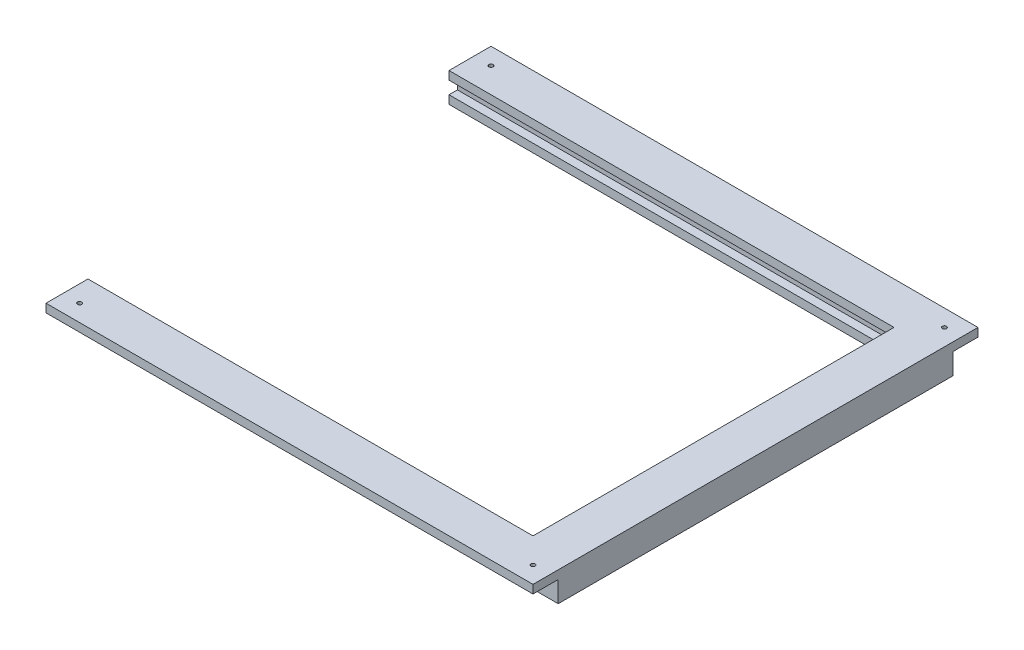
SolidWorks part; units mm, degrees
ref_plane "Спереди" through (0, 0, 0) normal (0, 0, 1) x (1, 0, 0)
ref_plane "Сверху" through (0, 0, 0) normal (0, 1, 0) x (1, 0, 0)
ref_plane "Справа" through (0, 0, 0) normal (1, 0, 0) x (0, 0, -1)
sketch "Эскиз1" plane through (0, 0, 0) normal (0, 1, 0) x (1, 0, 0)
  line L0 (50, -77.9215) -> (50, -607.9215)
  line L1 (-530, -77.9215) -> (50, -77.9215)
  line L2 (-530, -77.9215) -> (-530, -127.9215)
  line L3 (-530, -607.9215) -> (50, -607.9215)
  line L5 (-530, -127.9215) -> (0, -127.9215)
  line L7 (-530, -557.9215) -> (0, -557.9215)
  line L13 (-530, -557.9215) -> (-530, -607.9215)
  line L22 (0, -127.9215) -> (0, -557.9215)
  dimension "D1" = 580
  dimension "D12" = 50
  dimension "D2" = 530
  dimension "D3" = 50
  dimension "D4" = 50
  dimension "D9" = 50
  dimension "D8" = 77.9215
extrude "Бобышка-Вытянуть2" add sketch "Эскиз1" along normal blind 10
sketch "Эскиз2" plane through (0, 0, 0) normal (0, -1, 0) x (1, 0, 0)
  line L0 (-530, 127.9215) -> (0, 127.9215) construction
  line L5 (50, 607.9215) -> (50, 77.9215) construction
  line L6 (0, 557.9215) -> (-530, 557.9215) construction
  line L18 (50, 577.9215) -> (50, 107.9215)
  line L20 (10, 567.9215) -> (10, 117.9215)
  line L21 (-530, 77.9215) -> (-530, 127.9215) construction
  line L22 (50, 107.9215) -> (-530, 107.9215)
  line L24 (10, 117.9215) -> (-530, 117.9215)
  line L25 (-530, 107.9215) -> (-530, 117.9215)
  line L26 (-530, 557.9215) -> (-530, 607.9215) construction
  line L27 (50, 577.9215) -> (-530, 577.9215)
  line L29 (10, 567.9215) -> (-530, 567.9215)
  line L30 (-530, 577.9215) -> (-530, 567.9215)
  dimension "D1" = 40
  dimension "D2" = 10
  dimension "D3" = 10
  dimension "D4" = 10
  dimension "D5" = 10
extrude "Бобышка-Вытянуть3" add sketch "Эскиз2" along normal blind 15
sketch "Эскиз4" plane through (0, 10, 0) normal (0, 1, 0) x (1, 0, 0)
  line L0 (50, -77.9215) -> (-530, -77.9215) construction
  line L1 (-530, -77.9215) -> (-530, -127.9215) construction
  circle A0 centre (-510, -97.9215) radius 2.5
  dimension "D1" = 5
  dimension "D2" = 20
  dimension "D3" = 20
extrude "Вырез-Вытянуть1" cut sketch "Эскиз4" against normal through all
pattern_linear "Линейный массив2" count 2 spacing 540 along (1, 0, 0) count 2 spacing 490 along (0, 0, 1) of "Вырез-Вытянуть1"
sketch "Эскиз5" plane through (0, -15, 0) normal (0, -1, 0) x (1, 0, 0)
  line L8 (50, 577.9215) -> (-530, 577.9215)
  line L9 (-530, 577.9215) -> (-530, 557.9215)
  line L10 (-530, 557.9215) -> (0, 557.9215)
  line L11 (0, 557.9215) -> (0, 127.9215)
  line L12 (0, 127.9215) -> (-530, 127.9215)
  line L13 (-530, 127.9215) -> (-530, 107.9215)
  line L14 (-530, 107.9215) -> (50, 107.9215)
  line L15 (50, 107.9215) -> (50, 577.9215)
extrude "Бобышка-Вытянуть4" add sketch "Эскиз5" along normal blind 10
equation "\"Ширина груза\"= 420"
equation "\"Глубина груза\"= 490"
equation "\"Высота груза\"= 297"
equation "\"Ширина ячейки\"= \"Ширина груза\" + 10"
equation "\"Глубина ячейки\"= \"Глубина груза\" + 10"
equation "\"Высота ячейки\"= \"Высота груза\" + 10 + 13"
equation "\"Колво ячеек ширина\"= 2"
equation "\"Колво ячеек высота\"= 2"
equation "\"Толщина стенки\"= 10"
equation "\"Крепление дверцы\"= 5"
equation "\"Ширина рейки\"= \"Толщина шестерни\""
equation "\"Высота рейки\"= 20"
equation "\"Высота пола\"= 20"
equation "\"Колво полозьев\"= 5"
equation "\"Отступ рейки\"= 20"
equation "\"Глубина каретки\"= \"Глубина ячейки\" + 80"
equation "\"Длинна рейки\"= ( \"Ширина ячейки\" + \"Толщина стенки\" + \"Крепление дверцы\" ) * \"Колво ячеек ширина\" + \"Ширина ячейки выгрузки\" * \"Колво выгрузки\" + \"Толщина стенки\""
equation "\"Отступ шпильки\"= 20"
equation "\"Диаметр шпильки\"= 5"
equation "\"Длинна шпильки\"= ( \"Высота ячейки\" + \"Толщина стенки\" + \"Высота пола\" ) * \"Колво ячеек высота\" + ( \"Толщина стенки\" + \"Отступ рейки\" ) * 2"
equation "\"D2@Эскиз1\"=\"Ширина ячейки\" + \"Ширина пластины\" * 2 "
equation "\"D9@Эскиз1\"=\"Ширина пластины\""
equation "\"D3@Эскиз1\"=\"Ширина пластины\""
equation "\"D4@Эскиз1\"= \"Ширина пластины\""
equation "\"Ширина пластины\"= 50  "
equation "\"D1@Бобышка-Вытянуть2\"=\"Толщина стенки\""
equation "\"D1@Эскиз4\"= \"Диаметр шпильки\""
equation "\"D4@Линейный массив2\"=\"Ширина ячейки\" + \"Ширина пластины\" * 2  - \"Отступ шпильки\" * 2"
equation "\"D1@Эскиз1\"= \"Глубина каретки\""
equation "\"D3@Линейный массив2\"= \"Глубина каретки\" - \"Отступ шпильки\" * 2"
equation "\"D2@Эскиз4\"=\"Отступ шпильки\""
equation "\"D3@Эскиз4\"= \"Отступ шпильки\""
equation "\"D1@Эскиз2\"= \"Ширина пластины\" - \"Толщина стенки\""
equation "\"D2@Эскиз2\"= \"Толщина стенки\""
equation "\"D3@Эскиз2\"= \"Толщина стенки\""
equation "\"D4@Эскиз2\"= \"Толщина стенки\""
equation "\"D5@Эскиз2\"= \"Толщина стенки\""
equation "\"D1@Бобышка-Вытянуть4\"= \"Толщина стенки\""
equation "\"Вы\"=20"
equation "\"D1@Бобышка-Вытянуть3\"=\"Высота пола\" - 5"
equation "\"Высота зона выгрузки\"= \"Высота ячейки\" * 2 + \"Толщина стенки\" * 2"
equation "\"Колво выгрузки\"= 1"
equation "\"Ширина ячейки выгрузки\"= \"Ширина ячейки\" + \"Толщина стенки\" + \"Отступ крепления мотора фиксации\"*2"
equation "\"Отступ крепления мотора фиксации\" = 30"
equation "\"Мотор X ширина корпуса\"= 42.3"
equation "\"Мотор X высота корпуса\"= 42.3"
equation "\"Мотор X длина корпуса\"= 40"
equation "\"Мотор X вылет вала\"= 19.8"
equation "\"Мотор Y ширина корпуса\"= 42.3"
equation "\"Мотор Y высота корпуса\"= 42.3"
equation "\"Мотор Y длина корпуса\"= 48"
equation "\"Мотор Y вылет вала\"= 30"
equation "\"Мотор Z ширина корпуса\"= 42"
equation "\"Мотор Z высота корпуса\"= 42"
equation "\"Мотор Z длина корпуса\"= 40"
equation "\"Мотор Z вылет вала\"= 23"
equation "\"Мотор диаметр вала ПРЕДВ\"= 5"
equation "\"Мотор шаг крепления ПРЕДВ\"= 31"
equation "\"Мотор диаметр отверстий ПРЕДВ\"= 3"
equation "\"Мотор глубина отверстий ПРЕДВ\"= 4.5"
equation "\"Мотор диаметр буртика ПРЕДВ\"= 22"
equation "\"Мотор высота буртика ПРЕДВ\"= 2"
equation "\"Мотор диаметр шкива ПРЕДВ\"= 16"
equation "\"Мотор длина шкива ПРЕДВ\"= 12"
equation "\"Мотор отступ шкива ПРЕДВ\"= 5"
equation "\"Мотор X шаг градусов\"= 1.8"
equation "\"Мотор X ток А\"= 1.5"
equation "\"Мотор X сопротивление Ом\"= 1.3"
equation "\"Мотор X индуктивность мГн\"= 2"
equation "\"Мотор Y шаг градусов\"= 1.8"
equation "\"Мотор Y ток А\"= 2.2"
equation "\"Мотор Y сопротивление Ом\"= 0.9"
equation "\"Мотор Y индуктивность мГн\"= 2"
equation "\"Мотор Z шаг градусов\"= 1.8"
equation "\"Мотор Z ток А\"= 1"
equation "\"Мотор Z сопротивление Ом\"= 4"
equation "\"Мотор Z индуктивность мГн\"= 8"
equation "\"Мотор Y диаметр ротора\"= 25.78"
